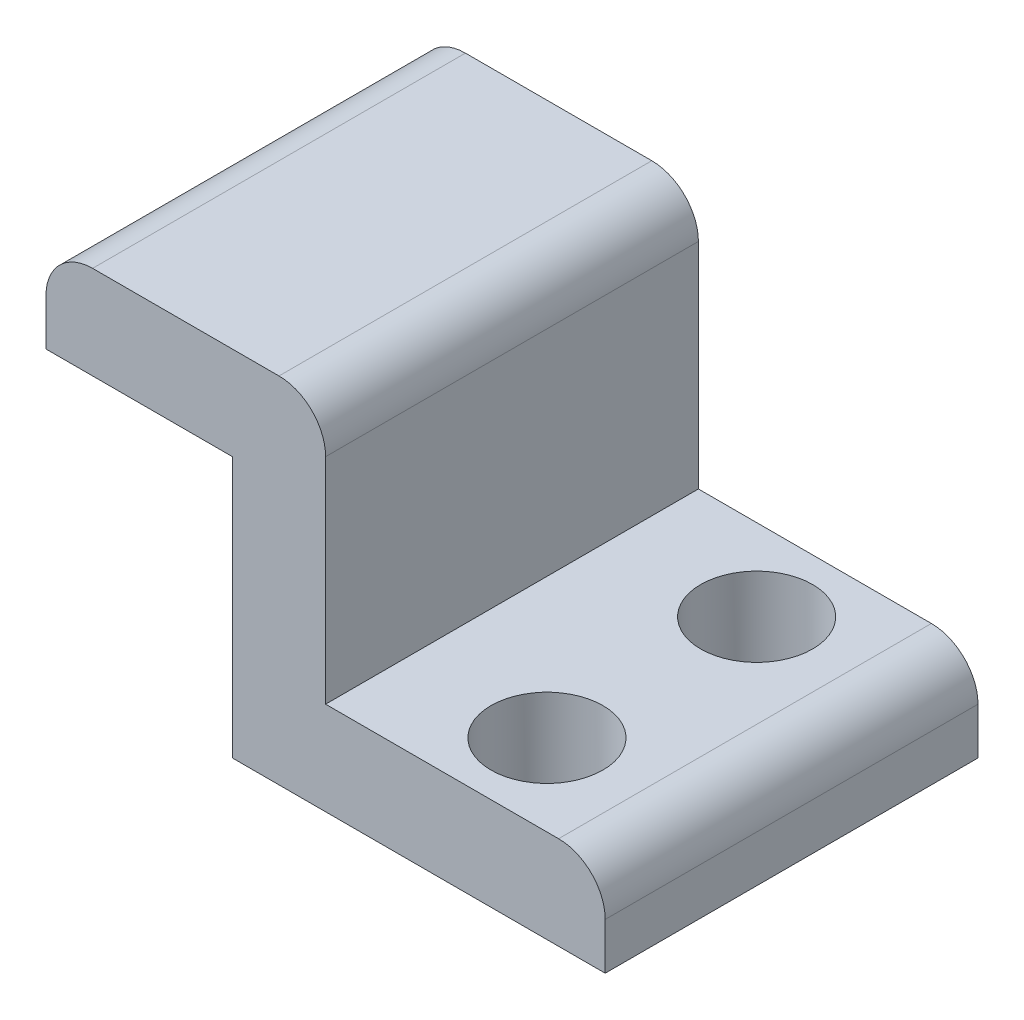
SolidWorks part; units mm, degrees
material "6061-T6 (SS)"
ref_plane "Front Plane" through (0, 0, 0) normal (0, 0, 1) x (1, 0, 0)
ref_plane "Top Plane" through (0, 0, 0) normal (0, 1, 0) x (1, 0, 0)
ref_plane "Right Plane" through (0, 0, 0) normal (1, 0, 0) x (0, 0, -1)
sketch "Sketch1" plane through (0, 0, 0) normal (0, 0, 1) x (1, 0, 0)
  line L0 (0, 0) -> (8, 0)
  line L1 (55, 0) -> (-55, 0) construction
  line L2 (8, 0) -> (8, 1)
  line L3 (7, 2) -> (2, 2)
  line L4 (2, 2) -> (2, 6.6)
  line L5 (1, 7.6) -> (-3, 7.6)
  line L6 (-4, 6.6) -> (-4, 5.6)
  line L7 (-4, 5.6) -> (0, 5.6)
  line L8 (0, -55) -> (0, 55) construction
  line L9 (0, 5.6) -> (0, 0)
  line L10 (0, 3.3245) -> (2, 3.3245) construction
  line L11 (-3.075, 7.6) -> (-3.075, 5.6) construction
  line L12 (3.5544, 2) -> (3.5544, 0) construction
  arc A0 (8, 1) -> (7, 2) centre (7, 1) ccw
  arc A1 (2, 6.6) -> (1, 7.6) centre (1, 6.6) ccw
  arc A3 (-3, 7.6) -> (-4, 6.6) centre (-3, 6.6) ccw
  point P26 (2, 2)
  dimension "D4" = 5
  dimension "D3" = 1
  dimension "D5" = 4
  dimension "D1" = 5.6
  dimension "D2" = 2
extrude "Boss-Extrude1" add sketch "Sketch1" along normal blind 8
ref_plane "Plane1" through (0, 12, 0) normal (0, 1, 0) x (1, 0, 0)
hole_wizard "M2 Clearance Hole2" positions "Sketch2" profile "Sketch3" hole size "M2" standard "ANSI Metric" end condition through all
sketch "Sketch2" plane through (0, 12, 0) normal (0, 1, 0) x (1, 0, 0)
  line L8 (8, 0) -> (0, 0)
  line L9 (8, -8) -> (8, 0)
  line L10 (0, -8) -> (8, -8)
  line L11 (0, 0) -> (0, -8)
  line L12 (8, 0) -> (2, 0)
  line L13 (8, -8) -> (8, 0)
  line L14 (2, -8) -> (8, -8)
  line L16 (5, 0) -> (5, -1.75) construction
  line L36 (2, -8) -> (2, 0) construction
  line L37 (2, -8) -> (2, 0)
  point P0 (5, -1.75)
  dimension "D2" = 1.75
  dimension "D1" = 0
sketch "Sketch3" plane through (5, 12, 1.75) normal (1, 0, 0) x (0, 0, 1)
  line L0 (0, 0) -> (0, 12)
  line L1 (0, 12) -> (1.2, 12)
  line L2 (1.2, 12) -> (1.2, 0)
  line L5 (1.2, 0) -> (0, 0)
  line L11 (0, -6.35) -> (0, 107.95) construction
  dimension "Thru Hole Dia." = 2.4
  dimension "Thru Hole Depth" = 12
hole_wizard "M2 Clearance Hole1" positions "Sketch4" profile "Sketch5" hole size "M2" standard "ANSI Metric" end condition through all
sketch "Sketch4" plane through (0, 12, 0) normal (0, 1, 0) x (1, 0, 0)
  line L9 (8, 0) -> (0, 0)
  line L10 (8, -8) -> (8, 0)
  line L11 (0, -8) -> (8, -8)
  line L12 (0, 0) -> (0, -8)
  line L13 (8, 0) -> (2, 0)
  line L14 (8, -8) -> (8, 0)
  line L15 (2, -8) -> (8, -8)
  line L19 (5, -6.25) -> (5, -8) construction
  line L65 (2, -8) -> (2, 0) construction
  line L66 (2, -8) -> (2, 0)
  point P0 (5, -6.25)
  dimension "D2" = 1.75
  dimension "D1" = 0
sketch "Sketch5" plane through (5, 12, 6.25) normal (1, 0, 0) x (0, 0, 1)
  line L0 (0, 0) -> (0, 12)
  line L1 (0, 12) -> (1.2, 12)
  line L2 (1.2, 12) -> (1.2, 0)
  line L5 (1.2, 0) -> (0, 0)
  line L11 (0, -6.35) -> (0, 107.95) construction
  dimension "Thru Hole Dia." = 2.4
  dimension "Thru Hole Depth" = 12
sketch "Sketch6" plane through (0, 0, 0) normal (0, 0, -1) x (-1, 0, 0)
  line L0 (-2, 2) -> (-2, 6.6) construction
  line L1 (8.6866, 11.5255) -> (-2, 11.5255)
  line L2 (8.6866, 11.5255) -> (8.6866, -5.2781)
  line L3 (8.6866, -5.2781) -> (-2, -5.2781)
  line L4 (-2, 11.5255) -> (-2, -5.2781)
extrude "Cut-Extrude1" [suppressed] cut sketch "Sketch6" against normal blind 6.5
